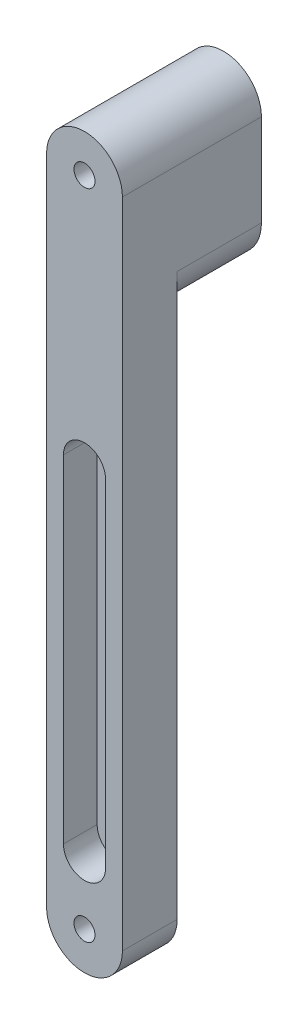
SolidWorks part; units mm, degrees
ref_plane "Front Plane" through (0, 0, 0) normal (0, 0, 1) x (1, 0, 0)
ref_plane "Top Plane" through (0, 0, 0) normal (0, 1, 0) x (1, 0, 0)
ref_plane "Right Plane" through (0, 0, 0) normal (1, 0, 0) x (0, 0, -1)
sketch "Sketch1" plane through (0, 0, 0) normal (0, 0, 1) x (1, 0, 0)
  line L0 (-9, 56.3943) -> (-9, -98.6057)
  line L1 (9, -98.6057) -> (9, 56.3943)
  circle A0 centre (0, 56.3943) radius 2.5
  circle A1 centre (0, -98.6057) radius 2.5
  arc A2 (9, 56.3943) -> (-9, 56.3943) centre (0, 56.3943) ccw
  arc A3 (-9, -98.6057) -> (9, -98.6057) centre (0, -98.6057) ccw
  dimension "D1" = 5
  dimension "D2" = 5
  dimension "D3" = 18
  dimension "D4" = 18
  dimension "D5" = 155
extrude "Extrude1" add sketch "Sketch1" along normal blind 13
sketch "Sketch2" plane through (0, 0, 13) normal (0, 0, 1) x (1, 0, 0)
  line L0 (-5, -3.6057) -> (-5, -83.6057)
  line L1 (5, -83.6057) -> (5, -3.6057)
  arc A0 (5, -3.6057) -> (-5, -3.6057) centre (0, -3.6057) ccw
  arc A1 (-5, -83.6057) -> (5, -83.6057) centre (0, -83.6057) ccw
  circle A2 centre (0, -98.6057) radius 2.5 construction
  dimension "D3" = 10
  dimension "D4" = 10
  dimension "D1" = 15
  dimension "D2" = 80
extrude "Extrude2" cut sketch "Sketch2" against normal blind 8
sketch "Sketch3" plane through (0, 0, 0) normal (0, 0, -1) x (-1, 0, 0)
  line L0 (-9, 56.3943) -> (-9, 24.5856)
  line L1 (-9, -98.6057) -> (-9, 56.3943) construction
  line L2 (-9, 24.5856) -> (9, 24.5856)
  line L3 (9, 56.3943) -> (9, -98.6057) construction
  line L4 (9, 24.5856) -> (9, 56.3943)
  arc A0 (9, 56.3943) -> (-9, 56.3943) centre (0, 56.3943) ccw
extrude "Extrude3" add sketch "Sketch3" along normal blind 20
fillet "Fillet1" radius 10 1 edges
fillet "Fillet2" radius 10 1 edges
sketch "Sketch4" plane through (0, 0, 13) normal (0, 0, 1) x (1, 0, 0)
  circle A0 centre (0, 56.3943) radius 2.5
extrude "Extrude4" cut sketch "Sketch4" against normal through all
